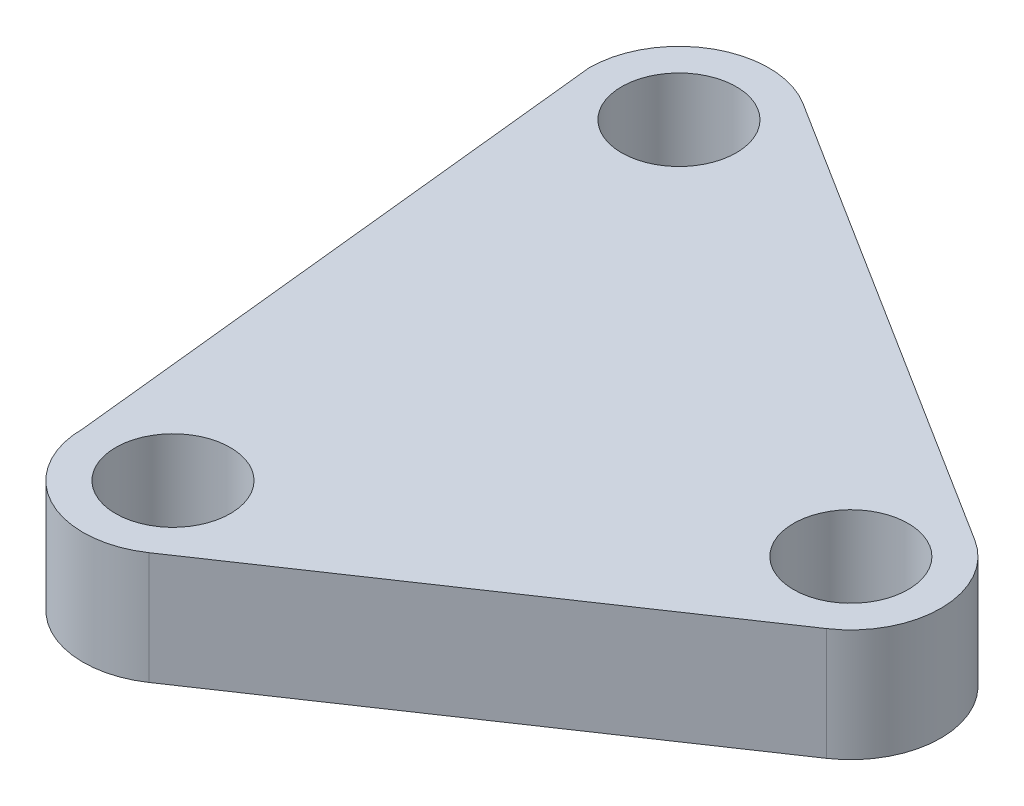
SolidWorks part; units mm, degrees
ref_plane "Front Plane" through (0, 0, 0) normal (0, 0, 1) x (1, 0, 0)
ref_plane "Top Plane" through (0, 0, 0) normal (0, 1, 0) x (1, 0, 0)
ref_plane "Right Plane" through (0, 0, 0) normal (1, 0, 0) x (0, 0, -1)
sketch "Sketch1" plane through (0, 0, 0) normal (0, 1, 0) x (1, 0, 0)
  line L0 (20.6457, -13) -> (0, 0)
  line L1 (0, 0) -> (2.6457, -25.15)
  line L2 (2.6457, -25.15) -> (20.6457, -13)
  line L3 (-4, 0) -> (-1.3543, -25.15)
  line L4 (22.8836, -16.3154) -> (4.8836, -28.4654)
  line L5 (2.1314, 3.3849) -> (22.777, -9.6151)
  circle A0 centre (0, 0) radius 2.55
  circle A1 centre (20.6457, -13) radius 2.55
  circle A2 centre (2.6457, -25.15) radius 2.55
  circle A3 centre (0, 0) radius 4
  circle A4 centre (20.6457, -13) radius 4
  circle A5 centre (2.6457, -25.15) radius 4
  dimension "D9" = 5.1
  dimension "D10" = 8
  dimension "D1" = 24.3976
  dimension "D2" = 25.2888
  dimension "D3" = 21.7169
  dimension "D4" = 61.986
  dimension "D5" = 51.797
  dimension "D6" = 66.217
  dimension "D7" = 0
  dimension "D8" = 13
extrude "Boss-Extrude1" add sketch "Sketch1" along normal blind 5 contours A5 L1 A3 L3 | A4 L5 A3 L0 | L0 A3 L3 L1 A0 | L1 A3 L0 A0 | A5 L2 A4 L0 A3 L1 | A5 L4 A4 L2 | A5 L2 A2 L1 | L2 A5 L1 A2 | A4 L0 A1 L2 | L0 A4 L2 A1 region at (17.4997, 0, 13.05) region at (17.9323, 0, 11.1628) region at (7.6971, 0, 12.6498) region at (11.4444, 0, 4.7188) region at (12.8335, 0, 20.8347) region at (1.6998, 0, 2.7304) region at (2.8316, 0, 1.6493) region at (6.3626, 0, 24.0129) region at (3.9841, 0, 22.278) region at (-0.7521, 0, 12.7933)
